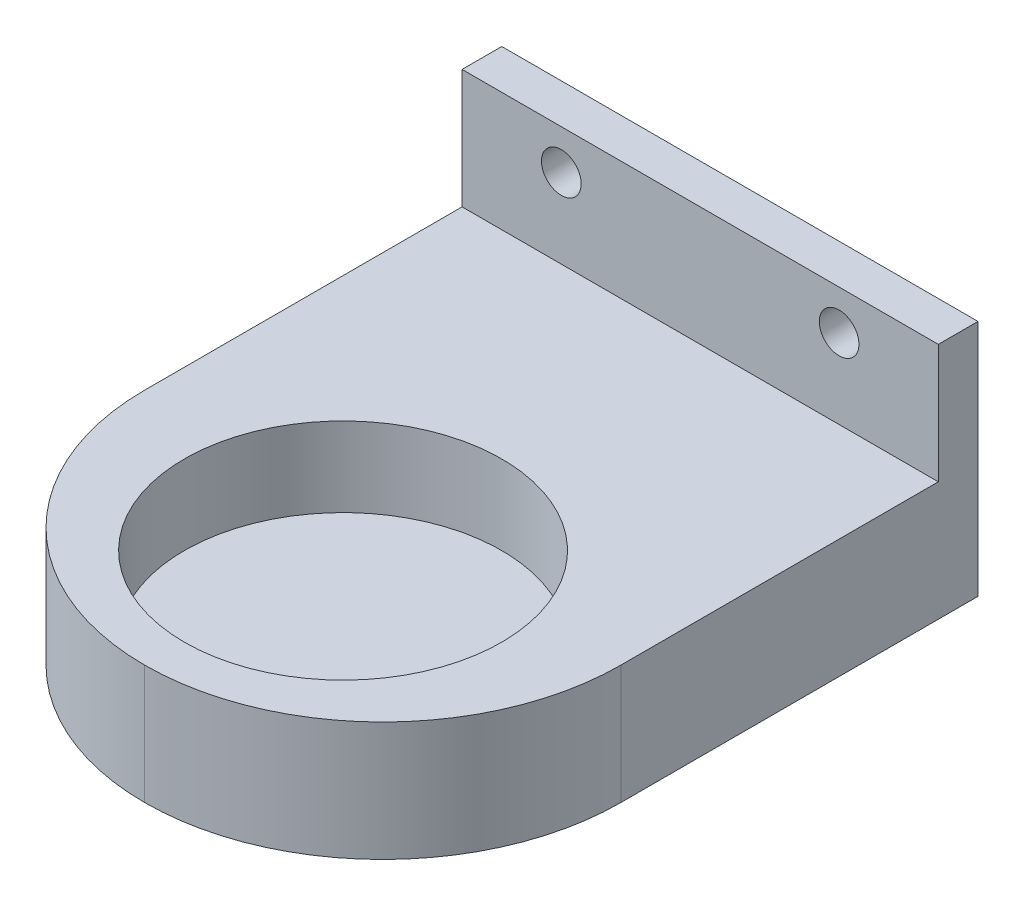
SolidWorks part; units mm, degrees
material "5052-H32"
ref_plane "Front Plane" through (0, 0, 0) normal (0, 0, 1) x (1, 0, 0)
ref_plane "Top Plane" through (0, 0, 0) normal (0, 1, 0) x (1, 0, 0)
ref_plane "Right Plane" through (0, 0, 0) normal (1, 0, 0) x (0, 0, -1)
sketch "Sketch1" plane through (0, 0, 0) normal (0, 0, 1) x (1, 0, 0)
  line L1 (-30, 15) -> (30, 15)
  line L2 (-30, 15) -> (-30, -15)
  line L3 (-30, -15) -> (30, -15)
  line L4 (30, 15) -> (30, -15)
  line L5 (-30, 15) -> (30, -15) construction
  line L6 (-30, -15) -> (30, 15) construction
  point P0 (0, 0)
  dimension "D1" = 30
  dimension "D2" = 60
extrude "Boss-Extrude1" add sketch "Sketch1" along normal blind 5
sketch "Sketch2" plane through (0, 0, 5) normal (0, 0, 1) x (1, 0, 0)
  line L0 (-30, 0) -> (30, 0)
  line L1 (-30, 15) -> (-30, -15) construction
  line L2 (30, -15) -> (30, 15) construction
  line L3 (30, 0) -> (30, -15)
  line L4 (30, -15) -> (-30, -15)
  line L5 (-30, -15) -> (-30, 0)
  dimension "D1" = 15
extrude "Boss-Extrude2" add sketch "Sketch2" along normal blind 70
sketch "Sketch3" plane through (0, 0, 0) normal (0, 1, 0) x (1, 0, 0)
  line L0 (30, -75) -> (30, -5) construction
  line L2 (30, -75) -> (-30, -75) construction
  circle A0 centre (0, -50) radius 20
  dimension "D1" = 40
  dimension "D2" = 25
  dimension "D3" = 30
extrude "Cut-Extrude1" cut sketch "Sketch3" against normal blind 10
sketch "Sketch4" plane through (0, 0, 0) normal (0, 0, -1) x (-1, 0, 0)
  line L0 (30, -15) -> (-30, -15) construction
  line L1 (30, 15) -> (30, -15) construction
  circle A0 centre (-17.5, 10) radius 2.5
  circle A1 centre (17.5, 10) radius 2.5
  circle A2 centre (17.5, -5) radius 2.5
  circle A3 centre (-17.5, -5) radius 2.5
  dimension "D1" = 5
  dimension "D2" = 35
  dimension "D3" = 15
  dimension "D4" = 10
  dimension "D5" = 12.5
extrude "Cut-Extrude2" cut sketch "Sketch4" against normal blind 5
fillet "Fillet1" radius 30 2 edges at (30, -7.5, 75) (-30, -7.5, 75)
